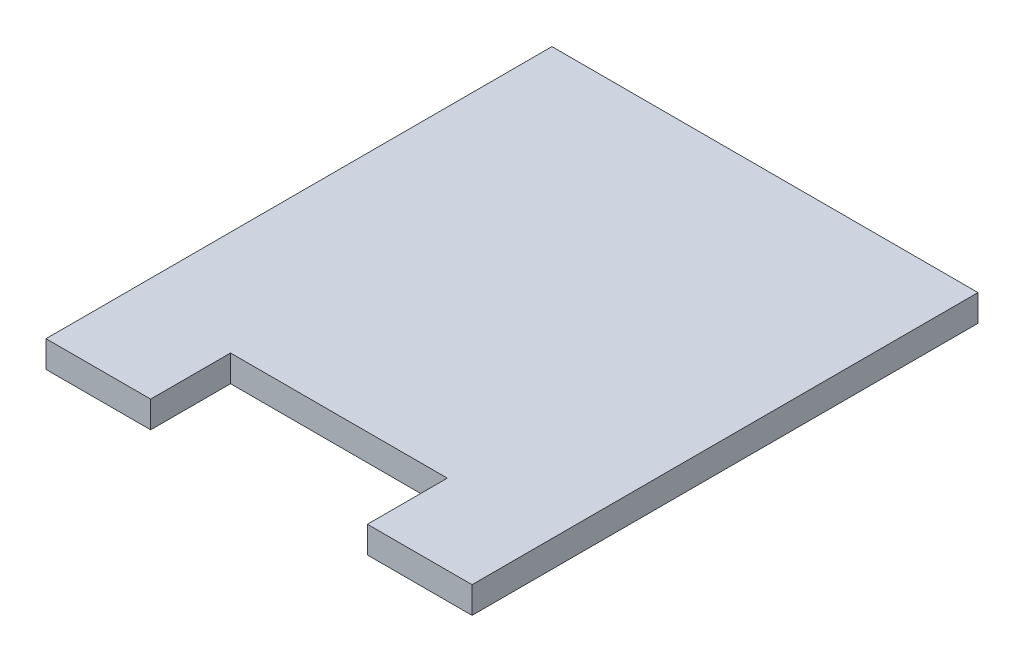
SolidWorks part; units mm, degrees
ref_plane "Front Plane" through (0, 0, 0) normal (0, 0, 1) x (1, 0, 0)
ref_plane "Top Plane" through (0, 0, 0) normal (0, 1, 0) x (1, 0, 0)
ref_plane "Right Plane" through (0, 0, 0) normal (1, 0, 0) x (0, 0, -1)
sketch "Sketch1" plane through (0, 0, 0) normal (0, 1, 0) x (1, 0, 0)
  line L14 (0, 0) -> (50.8, 0)
  line L15 (50.8, 0) -> (50.8, -60.325)
  line L16 (50.8, -60.325) -> (38.3223, -60.325)
  line L17 (38.3223, -60.325) -> (38.3223, -50.8)
  line L18 (38.3223, -50.8) -> (12.4777, -50.8)
  line L19 (12.4777, -50.8) -> (12.4778, -60.325)
  line L20 (12.4778, -60.325) -> (0, -60.325)
  line L21 (0, -60.325) -> (0, 0)
  dimension "D2" = 9.525
  dimension "D7" = 50.8
  dimension "D8" = 60.325
  dimension "D9" = 12.4778
  dimension "D10" = 12.4778
extrude "Boss-Extrude1" add sketch "Sketch1" along normal blind 3.175
